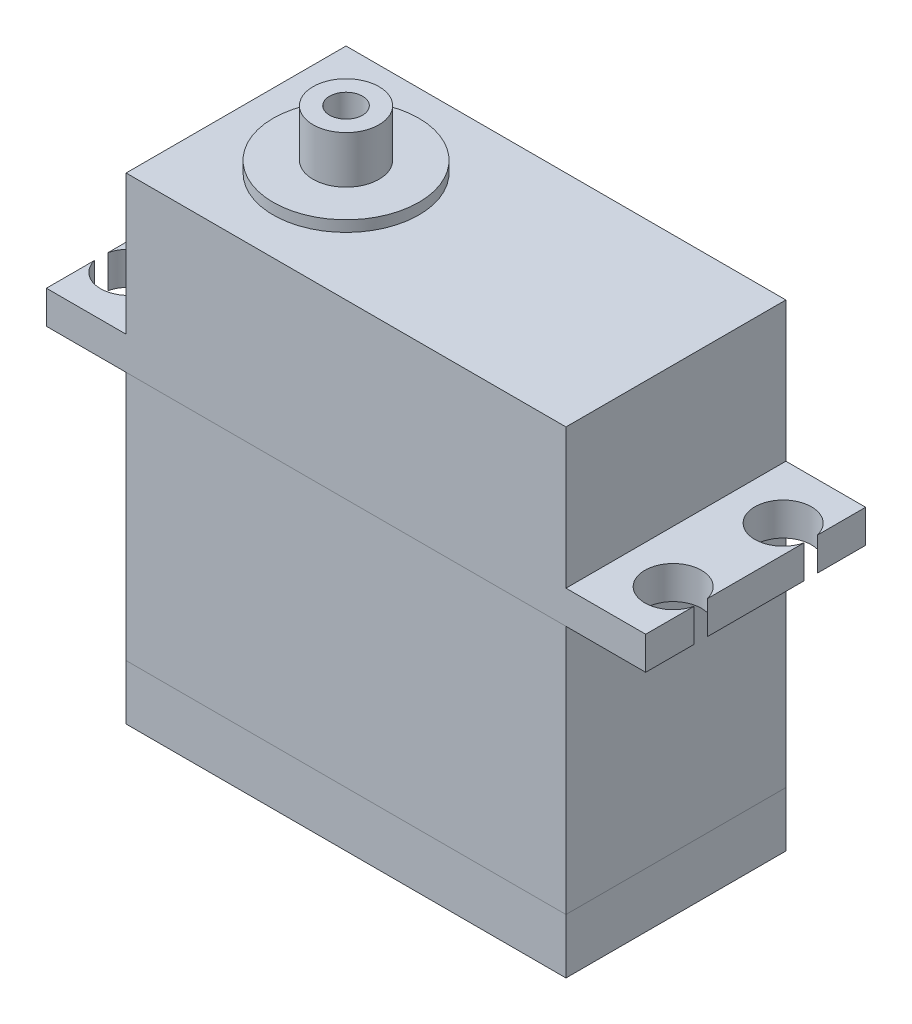
SolidWorks part; units mm, degrees
material "Nylon 101"
ref_plane "Front Plane" through (0, 0, 0) normal (0, 0, 1) x (1, 0, 0)
ref_plane "Top Plane" through (0, 0, 0) normal (0, 1, 0) x (1, 0, 0)
ref_plane "Right Plane" through (0, 0, 0) normal (1, 0, 0) x (0, 0, -1)
sketch "Sketch1" plane through (0, 0, 0) normal (0, 1, 0) x (1, 0, 0)
  line L1 (0, 0) -> (40, 0)
  line L2 (0, 0) -> (0, 20)
  line L3 (0, 20) -> (40, 20)
  line L4 (40, 0) -> (40, 20)
  dimension "D1" = 20
  dimension "D2" = 40
extrude "Boss-Extrude1" add sketch "Sketch1" along normal blind 12.7
sketch "Sketch2" plane through (0, 0, 0) normal (0, -1, 0) x (1, 0, 0)
  line L0 (40, -20) -> (0, -20) construction
  line L1 (-7.25, 0) -> (47.25, 0)
  line L2 (-7.25, 0) -> (-7.25, -20)
  line L3 (-7.25, -20) -> (47.25, -20)
  line L4 (47.25, 0) -> (47.25, -20)
  line L6 (0, 0) -> (40, 0) construction
  point P8 (20, 0)
  point P9 (20, 0)
  dimension "D1" = 54.5
extrude "Boss-Extrude2" add sketch "Sketch2" along normal blind 3
sketch "Sketch3" plane through (0, -3, 0) normal (0, -1, 0) x (1, 0, 0)
  line L4 (0, 0) -> (0, -20)
  line L5 (40, 0) -> (0, 0)
  line L6 (40, -20) -> (40, 0)
  line L7 (0, -20) -> (40, -20)
  line L8 (0, 0) -> (0, -20)
  line L9 (40, 0) -> (0, 0)
  line L10 (40, -20) -> (40, 0)
  line L11 (0, -20) -> (40, -20)
  dimension "D1" = 0
extrude "Boss-Extrude3" add sketch "Sketch3" along normal blind 22.7 separate body
sketch "Sketch4" plane through (0, -25.7, 0) normal (0, -1, 0) x (1, 0, 0)
  line L4 (0, -20) -> (40, -20)
  line L5 (40, -20) -> (40, 0)
  line L6 (40, 0) -> (0, 0)
  line L7 (0, 0) -> (0, -20)
  line L8 (0, -20) -> (40, -20)
  line L9 (40, -20) -> (40, 0)
  line L10 (40, 0) -> (0, 0)
  line L11 (0, 0) -> (0, -20)
  dimension "D1" = 0
extrude "Boss-Extrude5" add sketch "Sketch4" along normal blind 5 separate body
sketch "Sketch5" plane through (0, 12.7, 0) normal (0, 1, 0) x (1, 0, 0)
  line L0 (-7.25, 0) -> (-7.25, 20) construction
  circle A0 centre (10, 10) radius 6.625
  point P4 (-7.25, 10)
  dimension "D1" = 13.25
  dimension "D2" = 17.25
extrude "Boss-Extrude6" add sketch "Sketch5" along normal blind 1
sketch "Sketch6" plane through (0, 13.7, 0) normal (0, 1, 0) x (1, 0, 0)
  circle A0 centre (10, 10) radius 3
  circle A1 centre (10, 10) radius 6.625
  circle A2 centre (10, 10) radius 6.625 construction
  dimension "D2" = 6
  dimension "D1" = 0
extrude "Boss-Extrude7" add sketch "Sketch6" along normal blind 4.3 separate body
sketch "Sketch7" plane through (0, 0, 0) normal (0, 1, 0) x (1, 0, 0)
  line L0 (40, 20) -> (0, 20) construction
  line L1 (-4.75, 15) -> (44.75, 15) construction
  line L2 (-4.75, 15) -> (-4.75, 5) construction
  line L3 (-4.75, 5) -> (44.75, 5) construction
  line L4 (44.75, 15) -> (44.75, 5) construction
  line L5 (20, 20) -> (20, 0) construction
  line L6 (0, 0) -> (40, 0) construction
  circle A0 centre (-4.75, 5) radius 2.575
  circle A1 centre (-4.75, 15) radius 2.575
  circle A2 centre (44.75, 15) radius 2.575
  circle A3 centre (44.75, 5) radius 2.575
  point P10 (20, 20)
  point P11 (20, 15)
  point P16 (20, 10)
  point P17 (44.75, 10)
  dimension "D3" = 5.15
  dimension "D1" = 49.5
  dimension "D2" = 10
extrude "Cut-Extrude1" cut sketch "Sketch7" against normal up to next (3 mm away)
sketch "Sketch9" plane through (0, 18, 0) normal (0, 1, 0) x (1, 0, 0)
  circle A0 centre (10, 10) radius 1.5
  dimension "D1" = 3
extrude "Cut-Extrude3" cut sketch "Sketch9" against normal blind 4
chamfer "Chamfer1" [suppressed] distance 0.2 angle 45
sketch "Sketch10" [suppressed] plane through (40, 0, 0) normal (1, 0, 0) x (0, 0, -1)
  line L1 (7, -25.7) -> (13, -25.7)
  line L2 (7, -25.7) -> (7, -28.7)
  line L3 (7, -28.7) -> (13, -28.7)
  line L4 (13, -25.7) -> (13, -28.7)
  line L5 (20, -25.7) -> (0, -25.7) construction
  point P9 (10, -25.7)
  point P10 (10, -25.7)
  dimension "D1" = 3
  dimension "D2" = 6
extrude "Boss-Extrude8" [suppressed] add sketch "Sketch10" against normal blind 5 from surface separate body starting at face at (0, -28.2, -10)
sketch "Sketch8" [suppressed] plane through (0, 18, 0) normal (0, 1, 0) x (1, 0, 0)
  line L0 (10, 10) -> (10, 13) construction
  line L1 (9.675, 13) -> (10.325, 13)
  line L2 (10.325, 13) -> (10, 12.7)
  line L3 (10, 12.7) -> (9.675, 13)
  line L4 (10.6715, 12.6152) -> (10.4313, 12.9866)
  line L5 (10.4313, 12.9866) -> (11.0609, 12.8249)
  line L6 (11.0609, 12.8249) -> (10.6715, 12.6152)
  line L7 (11.3007, 12.366) -> (11.1605, 12.7855)
  line L8 (11.1605, 12.7855) -> (11.7301, 12.4724)
  line L9 (11.7301, 12.4724) -> (11.3007, 12.366)
  line L10 (11.8483, 11.9682) -> (11.8167, 12.4094)
  line L11 (11.8167, 12.4094) -> (12.2906, 11.9644)
  line L12 (12.2906, 11.9644) -> (11.8483, 11.9682)
  line L13 (12.2797, 11.4467) -> (12.3588, 11.8819)
  line L14 (12.3588, 11.8819) -> (12.7071, 11.3331)
  line L15 (12.7071, 11.3331) -> (12.2797, 11.4467)
  line L16 (12.5679, 10.8343) -> (12.7527, 11.2361)
  line L17 (12.7527, 11.2361) -> (12.9536, 10.618)
  line L18 (12.9536, 10.618) -> (12.5679, 10.8343)
  line L19 (12.6947, 10.1695) -> (12.9737, 10.5127)
  line L20 (12.9737, 10.5127) -> (13.0145, 9.864)
  line L21 (13.0145, 9.864) -> (12.6947, 10.1695)
  line L22 (12.6522, 9.4941) -> (13.0078, 9.7571)
  line L23 (13.0078, 9.7571) -> (12.886, 9.1186)
  line L24 (12.886, 9.1186) -> (12.6522, 9.4941)
  line L25 (12.443, 8.8504) -> (12.8529, 9.0167)
  line L26 (12.8529, 9.0167) -> (12.5761, 8.4286)
  line L27 (12.5761, 8.4286) -> (12.443, 8.8504)
  line L28 (12.0804, 8.279) -> (12.5187, 8.3381)
  line L29 (12.5187, 8.3381) -> (12.1044, 7.8373)
  line L30 (12.1044, 7.8373) -> (12.0804, 8.279)
  line L31 (11.587, 7.8157) -> (12.0263, 7.764)
  line L32 (12.0263, 7.764) -> (11.5004, 7.3819)
  line L33 (11.5004, 7.3819) -> (11.587, 7.8157)
  line L34 (10.9939, 7.4896) -> (11.4066, 7.3303)
  line L35 (11.4066, 7.3303) -> (10.8022, 7.091)
  line L36 (10.8022, 7.091) -> (10.9939, 7.4896)
  line L37 (10.3384, 7.3213) -> (10.6984, 7.0644)
  line L38 (10.6984, 7.0644) -> (10.0536, 6.9829)
  line L39 (10.0536, 6.9829) -> (10.3384, 7.3213)
  line L40 (9.6616, 7.3213) -> (9.9464, 6.9829)
  line L41 (9.9464, 6.9829) -> (9.3016, 7.0644)
  line L42 (9.3016, 7.0644) -> (9.6616, 7.3213)
  line L43 (9.0061, 7.4896) -> (9.1978, 7.091)
  line L44 (9.1978, 7.091) -> (8.5934, 7.3303)
  line L45 (8.5934, 7.3303) -> (9.0061, 7.4896)
  line L46 (8.413, 7.8157) -> (8.4996, 7.3819)
  line L47 (8.4996, 7.3819) -> (7.9737, 7.764)
  line L48 (7.9737, 7.764) -> (8.413, 7.8157)
  line L49 (7.9196, 8.279) -> (7.8956, 7.8373)
  line L50 (7.8956, 7.8373) -> (7.4813, 8.3381)
  line L51 (7.4813, 8.3381) -> (7.9196, 8.279)
  line L52 (7.557, 8.8504) -> (7.4239, 8.4286)
  line L53 (7.4239, 8.4286) -> (7.1471, 9.0167)
  line L54 (7.1471, 9.0167) -> (7.557, 8.8504)
  line L55 (7.3478, 9.4941) -> (7.114, 9.1186)
  line L56 (7.114, 9.1186) -> (6.9922, 9.7571)
  line L57 (6.9922, 9.7571) -> (7.3478, 9.4941)
  line L58 (7.3053, 10.1695) -> (6.9855, 9.864)
  line L59 (6.9855, 9.864) -> (7.0263, 10.5127)
  line L60 (7.0263, 10.5127) -> (7.3053, 10.1695)
  line L61 (7.4321, 10.8343) -> (7.0464, 10.618)
  line L62 (7.0464, 10.618) -> (7.2473, 11.2361)
  line L63 (7.2473, 11.2361) -> (7.4321, 10.8343)
  line L64 (7.7203, 11.4467) -> (7.2929, 11.3331)
  line L65 (7.2929, 11.3331) -> (7.6412, 11.8819)
  line L66 (7.6412, 11.8819) -> (7.7203, 11.4467)
  line L67 (8.1517, 11.9682) -> (7.7094, 11.9644)
  line L68 (7.7094, 11.9644) -> (8.1833, 12.4094)
  line L69 (8.1833, 12.4094) -> (8.1517, 11.9682)
  line L70 (8.6993, 12.366) -> (8.2699, 12.4724)
  line L71 (8.2699, 12.4724) -> (8.8395, 12.7855)
  line L72 (8.8395, 12.7855) -> (8.6993, 12.366)
  line L73 (9.3285, 12.6152) -> (8.9391, 12.8249)
  line L74 (8.9391, 12.8249) -> (9.5687, 12.9866)
  line L75 (9.5687, 12.9866) -> (9.3285, 12.6152)
  circle A0 centre (10, 10) radius 3 construction
  point P7 (10, 13)
  point P84 (10, 10)
  dimension "D1" = 0.3
  dimension "D2" = 0.65
  dimension "D3" = 25
extrude "Cut-Extrude2" [suppressed] cut sketch "Sketch8" against normal blind 3.3
sketch "Sketch11" [suppressed] plane through (0, 12.7, 0) normal (0, 1, 0) x (1, 0, 0)
  line L0 (20, 20) -> (20, 0) construction
  line L1 (40, 20) -> (0, 20) construction
  line L2 (0, 0) -> (40, 0) construction
  line L3 (0, 10) -> (40, 10) construction
  line L4 (0, 20) -> (0, 0) construction
  line L5 (40, 0) -> (40, 20) construction
  line L6 (35.8, 2.1) -> (35.8, 0)
  line L7 (35.8, 0) -> (40, 0)
  line L9 (37.9, 4.2) -> (40, 4.2)
  line L10 (40, 0) -> (40, 20) construction
  line L11 (40, 4.2) -> (40, 0)
  line L12 (37.9, 15.8) -> (40, 15.8)
  line L13 (40, 15.8) -> (40, 20)
  line L14 (35.8, 20) -> (40, 20)
  line L15 (35.8, 17.9) -> (35.8, 20)
  line L16 (2.1, 4.2) -> (0, 4.2)
  line L17 (0, 4.2) -> (0, 0)
  line L18 (4.2, 0) -> (0, 0)
  line L19 (4.2, 2.1) -> (4.2, 0)
  line L20 (4.2, 17.9) -> (4.2, 20)
  line L21 (4.2, 20) -> (0, 20)
  line L22 (0, 15.8) -> (0, 20)
  line L23 (2.1, 15.8) -> (0, 15.8)
  arc A0 (37.9, 4.2) -> (35.8, 2.1) centre (37.9, 2.1) ccw
  arc A1 (37.9, 15.8) -> (35.8, 17.9) centre (37.9, 17.9) cw
  arc A2 (2.1, 4.2) -> (4.2, 2.1) centre (2.1, 2.1) cw
  arc A3 (2.1, 15.8) -> (4.2, 17.9) centre (2.1, 17.9) ccw
  dimension "D1" = 4.2
extrude "Cut-Extrude4" [suppressed] cut sketch "Sketch11" against normal blind 1.75
sketch "Sketch13" [suppressed] plane through (0, -30.7, 0) normal (0, -1, 0) x (1, 0, 0)
  line L0 (37.9, -15.8) -> (40, -15.8) construction
  line L1 (40, -15.8) -> (40, -20) construction
  line L2 (40, -20) -> (35.8, -20) construction
  line L3 (35.8, -20) -> (35.8, -17.9) construction
  line L4 (35.8, -2.1) -> (35.8, 0) construction
  line L5 (35.8, 0) -> (40, 0) construction
  line L6 (40, 0) -> (40, -4.2) construction
  line L7 (40, -4.2) -> (37.9, -4.2) construction
  line L8 (2.1, -4.2) -> (0, -4.2) construction
  line L9 (0, -4.2) -> (0, 0) construction
  line L10 (0, 0) -> (4.2, 0) construction
  line L11 (4.2, 0) -> (4.2, -2.1) construction
  line L12 (4.2, -17.9) -> (4.2, -20) construction
  line L13 (4.2, -20) -> (0, -20) construction
  line L14 (0, -20) -> (0, -15.8) construction
  line L15 (0, -15.8) -> (2.1, -15.8) construction
  line L16 (37.9, -15.8) -> (40, -15.8)
  line L17 (40, -15.8) -> (40, -20)
  line L18 (40, -20) -> (35.8, -20)
  line L19 (35.8, -20) -> (35.8, -17.9)
  line L20 (35.8, -2.1) -> (35.8, 0)
  line L21 (35.8, 0) -> (40, 0)
  line L22 (40, 0) -> (40, -4.2)
  line L23 (40, -4.2) -> (37.9, -4.2)
  line L24 (2.1, -4.2) -> (0, -4.2)
  line L25 (0, -4.2) -> (0, 0)
  line L26 (0, 0) -> (4.2, 0)
  line L27 (4.2, 0) -> (4.2, -2.1)
  line L28 (4.2, -17.9) -> (4.2, -20)
  line L29 (4.2, -20) -> (0, -20)
  line L30 (0, -20) -> (0, -15.8)
  line L31 (0, -15.8) -> (2.1, -15.8)
  arc A0 (37.9, -15.8) -> (35.8, -17.9) centre (37.9, -17.9) ccw construction
  arc A1 (35.8, -2.1) -> (37.9, -4.2) centre (37.9, -2.1) ccw construction
  arc A2 (2.1, -4.2) -> (4.2, -2.1) centre (2.1, -2.1) ccw construction
  arc A3 (4.2, -17.9) -> (2.1, -15.8) centre (2.1, -17.9) ccw construction
  arc A4 (37.9, -15.8) -> (35.8, -17.9) centre (37.9, -17.9) ccw
  arc A5 (35.8, -2.1) -> (37.9, -4.2) centre (37.9, -2.1) ccw
  arc A6 (2.1, -4.2) -> (4.2, -2.1) centre (2.1, -2.1) ccw
  arc A7 (4.2, -17.9) -> (2.1, -15.8) centre (2.1, -17.9) ccw
extrude "Cut-Extrude6" [suppressed] cut sketch "Sketch13" against normal blind 1.75
sketch "Sketch12" [suppressed] plane through (0, 12.7, 0) normal (0, 1, 0) x (1, 0, 0)
  line L0 (0, 10) -> (40, 10) construction
  line L1 (0, 15.8) -> (0, 4.2) construction
  line L2 (40, 4.2) -> (40, 15.8) construction
  line L3 (35.8, 20) -> (4.2, 20) construction
  line L4 (13, 20) -> (27, 20)
  line L5 (13, 20) -> (13, 18.75)
  line L6 (13, 18.75) -> (27, 18.75)
  line L7 (27, 20) -> (27, 18.75)
  line L8 (13, 1.25) -> (27, 1.25)
  line L9 (27, 0) -> (27, 1.25)
  line L10 (13, 0) -> (27, 0)
  line L11 (13, 0) -> (13, 1.25)
  point P12 (20, 20)
  point P13 (20, 10)
  dimension "D1" = 1.25
  dimension "D2" = 14
extrude "Cut-Extrude5" [suppressed] cut sketch "Sketch12" against normal blind 1.25
sketch "Sketch14" [suppressed] plane through (0, -30.7, 0) normal (0, -1, 0) x (1, 0, 0)
  line L0 (13, -20) -> (13, -18.75) construction
  line L1 (13, -18.75) -> (27, -18.75) construction
  line L2 (27, -18.75) -> (27, -20) construction
  line L3 (27, -20) -> (13, -20) construction
  line L4 (13, -1.25) -> (13, 0) construction
  line L5 (13, 0) -> (27, 0) construction
  line L6 (27, 0) -> (27, -1.25) construction
  line L7 (27, -1.25) -> (13, -1.25) construction
  line L8 (13, -20) -> (13, -18.75)
  line L9 (13, -18.75) -> (27, -18.75)
  line L10 (27, -18.75) -> (27, -20)
  line L11 (27, -20) -> (13, -20)
  line L12 (13, -1.25) -> (13, 0)
  line L13 (13, 0) -> (27, 0)
  line L14 (27, 0) -> (27, -1.25)
  line L15 (27, -1.25) -> (13, -1.25)
extrude "Cut-Extrude7" [suppressed] cut sketch "Sketch14" against normal blind 1.25
chamfer "Chamfer2" [suppressed] distance 1.25 angle 45
chamfer "Chamfer3" [suppressed] distance 1.25 angle 45
fillet "Fillet1" [suppressed] radius 1.25
chamfer "Chamfer5" [suppressed] distance 0.3 angle 45
fillet "Fillet2" [suppressed] radius 1.25
chamfer "Chamfer6" [suppressed] distance 0.3 angle 45
fillet "Fillet3" [suppressed] radius 1
fillet "Fillet4" [suppressed] radius 1
fillet "Fillet5" [suppressed] radius 1
sketch "Sketch15" [suppressed] plane through (0, 10.95, 0) normal (0, 1, 0) x (1, 0, 0)
  line L0 (40, 15.8) -> (40, 19) construction
  line L1 (39, 20) -> (35.8, 20) construction
  line L2 (35.8, 20) -> (35.8, 17.9) construction
  line L3 (37.9, 15.8) -> (40, 15.8) construction
  line L4 (4.2, 20) -> (1, 20) construction
  line L5 (0, 19) -> (0, 15.8) construction
  line L6 (0, 15.8) -> (2.1, 15.8) construction
  line L7 (4.2, 17.9) -> (4.2, 20) construction
  line L8 (0, 4.2) -> (0, 1) construction
  line L9 (1, 0) -> (4.2, 0) construction
  line L10 (4.2, 0) -> (4.2, 2.1) construction
  line L11 (2.1, 4.2) -> (0, 4.2) construction
  line L12 (35.8, 0) -> (39, 0) construction
  line L13 (40, 1) -> (40, 4.2) construction
  line L14 (40, 4.2) -> (37.9, 4.2) construction
  line L15 (35.8, 2.1) -> (35.8, 0) construction
  line L16 (40, 15.8) -> (40, 19) construction
  line L17 (39, 20) -> (35.8, 20) construction
  line L18 (35.8, 20) -> (35.8, 17.9) construction
  line L19 (37.9, 15.8) -> (40, 15.8) construction
  line L20 (4.2, 20) -> (1, 20) construction
  line L21 (0, 19) -> (0, 15.8) construction
  line L22 (0, 15.8) -> (2.1, 15.8) construction
  line L23 (4.2, 17.9) -> (4.2, 20) construction
  line L24 (0, 4.2) -> (0, 1) construction
  line L25 (1, 0) -> (4.2, 0) construction
  line L26 (4.2, 0) -> (4.2, 2.1) construction
  line L27 (2.1, 4.2) -> (0, 4.2) construction
  line L28 (35.8, 0) -> (39, 0) construction
  line L29 (40, 1) -> (40, 4.2) construction
  line L30 (40, 4.2) -> (37.9, 4.2) construction
  line L31 (35.8, 2.1) -> (35.8, 0) construction
  arc A0 (40, 19) -> (39, 20) centre (39, 19) ccw construction
  arc A1 (35.8, 17.9) -> (37.9, 15.8) centre (37.9, 17.9) ccw construction
  arc A2 (1, 20) -> (0, 19) centre (1, 19) ccw construction
  arc A3 (2.1, 15.8) -> (4.2, 17.9) centre (2.1, 17.9) ccw construction
  arc A4 (0, 1) -> (1, 0) centre (1, 1) ccw construction
  arc A5 (4.2, 2.1) -> (2.1, 4.2) centre (2.1, 2.1) ccw construction
  arc A6 (39, 0) -> (40, 1) centre (39, 1) ccw construction
  arc A7 (37.9, 4.2) -> (35.8, 2.1) centre (37.9, 2.1) ccw construction
  arc A8 (40, 19) -> (39, 20) centre (39, 19) ccw construction
  arc A9 (35.8, 17.9) -> (37.9, 15.8) centre (37.9, 17.9) ccw construction
  arc A10 (1, 20) -> (0, 19) centre (1, 19) ccw construction
  arc A11 (2.1, 15.8) -> (4.2, 17.9) centre (2.1, 17.9) ccw construction
  arc A12 (0, 1) -> (1, 0) centre (1, 1) ccw construction
  arc A13 (4.2, 2.1) -> (2.1, 4.2) centre (2.1, 2.1) ccw construction
  arc A14 (39, 0) -> (40, 1) centre (39, 1) ccw construction
  arc A15 (37.9, 4.2) -> (35.8, 2.1) centre (37.9, 2.1) ccw construction
  circle A16 centre (2.1, 2.1) radius 1.875
  circle A17 centre (2.1, 17.9) radius 1.875
  circle A18 centre (37.9, 17.9) radius 1.875
  circle A19 centre (37.9, 2.1) radius 1.875
  dimension "D1" = 3.75
extrude "Boss-Extrude10" [suppressed] add sketch "Sketch15" along normal blind 1.25 separate body
sketch "Sketch16" [suppressed] plane through (0, -28.95, 0) normal (0, -1, 0) x (1, 0, 0)
  circle A0 centre (2.1, -2.1) radius 1.875 construction
  circle A1 centre (37.9, -2.1) radius 1.875 construction
  circle A2 centre (37.9, -17.9) radius 1.875 construction
  circle A3 centre (2.1, -17.9) radius 1.875 construction
  circle A4 centre (2.1, -2.1) radius 1.875
  circle A5 centre (37.9, -2.1) radius 1.875
  circle A6 centre (37.9, -17.9) radius 1.875
  circle A7 centre (2.1, -17.9) radius 1.875
extrude "Boss-Extrude12" [suppressed] add sketch "Sketch16" along normal blind 1.25 separate body
chamfer "Chamfer8" [suppressed] distance 0.15 angle 45
sketch "Sketch18" [suppressed] plane through (0, 12.2, 0) normal (0, 1, 0) x (1, 0, 0)
  line L0 (0.3, 10) -> (39.7, 10) construction
  line L1 (0.3, 15.5) -> (0.3, 4.5) construction
  line L2 (39.7, 4.5) -> (39.7, 15.5) construction
  line L3 (20, 18.75) -> (20, 1.25) construction
  line L4 (14.25, 18.75) -> (25.75, 18.75) construction
  line L5 (25.75, 1.25) -> (14.25, 1.25) construction
  line L6 (2.7351, 3.2) -> (3.3702, 2.1)
  line L7 (3.3702, 17.9) -> (2.7351, 19)
  line L8 (2.7351, 19) -> (1.4649, 19)
  line L9 (1.4649, 19) -> (0.8298, 17.9)
  line L10 (0.8298, 17.9) -> (1.4649, 16.8)
  line L11 (1.4649, 16.8) -> (2.7351, 16.8)
  line L12 (2.7351, 16.8) -> (3.3702, 17.9)
  line L13 (1.4649, 3.2) -> (2.7351, 3.2)
  line L14 (0.8298, 2.1) -> (1.4649, 3.2)
  line L15 (1.4649, 1) -> (0.8298, 2.1)
  line L16 (2.7351, 1) -> (1.4649, 1)
  line L17 (3.3702, 2.1) -> (2.7351, 1)
  line L18 (38.5351, 3.2) -> (37.2649, 3.2)
  line L19 (39.1702, 2.1) -> (38.5351, 3.2)
  line L20 (38.5351, 1) -> (39.1702, 2.1)
  line L21 (37.2649, 1) -> (38.5351, 1)
  line L22 (36.6298, 2.1) -> (37.2649, 1)
  line L23 (37.2649, 3.2) -> (36.6298, 2.1)
  line L24 (37.2649, 16.8) -> (36.6298, 17.9)
  line L25 (38.5351, 16.8) -> (37.2649, 16.8)
  line L26 (39.1702, 17.9) -> (38.5351, 16.8)
  line L27 (38.5351, 19) -> (39.1702, 17.9)
  line L28 (37.2649, 19) -> (38.5351, 19)
  line L29 (36.6298, 17.9) -> (37.2649, 19)
  circle A1 centre (2.1, 17.9) radius 1.1 construction
  circle A2 centre (2.1, 17.9) radius 1.875
  circle A3 centre (2.1, 17.9) radius 1.875 construction
  dimension "D1" = 0
  dimension "D2" = 2.2
extrude "Cut-Extrude8" [suppressed] cut sketch "Sketch18" against normal blind 1.22
sketch "Sketch19" [suppressed] plane through (0, -30.2, 0) normal (0, -1, 0) x (1, 0, 0)
  line L0 (37.2649, -16.8) -> (38.5351, -16.8) construction
  line L1 (38.5351, -16.8) -> (39.1702, -17.9) construction
  line L2 (39.1702, -17.9) -> (38.5351, -19) construction
  line L3 (38.5351, -19) -> (37.2649, -19) construction
  line L4 (37.2649, -19) -> (36.6298, -17.9) construction
  line L5 (36.6298, -17.9) -> (37.2649, -16.8) construction
  line L6 (39.1702, -2.1) -> (38.5351, -3.2) construction
  line L7 (38.5351, -3.2) -> (37.2649, -3.2) construction
  line L8 (37.2649, -3.2) -> (36.6298, -2.1) construction
  line L9 (36.6298, -2.1) -> (37.2649, -1) construction
  line L10 (37.2649, -1) -> (38.5351, -1) construction
  line L11 (38.5351, -1) -> (39.1702, -2.1) construction
  line L12 (2.7351, -3.2) -> (1.4649, -3.2) construction
  line L13 (1.4649, -3.2) -> (0.8298, -2.1) construction
  line L14 (0.8298, -2.1) -> (1.4649, -1) construction
  line L15 (1.4649, -1) -> (2.7351, -1) construction
  line L16 (2.7351, -1) -> (3.3702, -2.1) construction
  line L17 (3.3702, -2.1) -> (2.7351, -3.2) construction
  line L18 (2.7351, -16.8) -> (3.3702, -17.9) construction
  line L19 (3.3702, -17.9) -> (2.7351, -19) construction
  line L20 (2.7351, -19) -> (1.4649, -19) construction
  line L21 (1.4649, -19) -> (0.8298, -17.9) construction
  line L22 (0.8298, -17.9) -> (1.4649, -16.8) construction
  line L23 (1.4649, -16.8) -> (2.7351, -16.8) construction
  line L24 (37.2649, -16.8) -> (38.5351, -16.8)
  line L25 (38.5351, -16.8) -> (39.1702, -17.9)
  line L26 (39.1702, -17.9) -> (38.5351, -19)
  line L27 (38.5351, -19) -> (37.2649, -19)
  line L28 (37.2649, -19) -> (36.6298, -17.9)
  line L29 (36.6298, -17.9) -> (37.2649, -16.8)
  line L30 (39.1702, -2.1) -> (38.5351, -3.2)
  line L31 (38.5351, -3.2) -> (37.2649, -3.2)
  line L32 (37.2649, -3.2) -> (36.6298, -2.1)
  line L33 (36.6298, -2.1) -> (37.2649, -1)
  line L34 (37.2649, -1) -> (38.5351, -1)
  line L35 (38.5351, -1) -> (39.1702, -2.1)
  line L36 (2.7351, -3.2) -> (1.4649, -3.2)
  line L37 (1.4649, -3.2) -> (0.8298, -2.1)
  line L38 (0.8298, -2.1) -> (1.4649, -1)
  line L39 (1.4649, -1) -> (2.7351, -1)
  line L40 (2.7351, -1) -> (3.3702, -2.1)
  line L41 (3.3702, -2.1) -> (2.7351, -3.2)
  line L42 (2.7351, -16.8) -> (3.3702, -17.9)
  line L43 (3.3702, -17.9) -> (2.7351, -19)
  line L44 (2.7351, -19) -> (1.4649, -19)
  line L45 (1.4649, -19) -> (0.8298, -17.9)
  line L46 (0.8298, -17.9) -> (1.4649, -16.8)
  line L47 (1.4649, -16.8) -> (2.7351, -16.8)
extrude "Cut-Extrude9" [suppressed] cut sketch "Sketch19" against normal blind 1.22
sketch "Sketch23" [suppressed] plane through (0, 18, 0) normal (0, 1, 0) x (1, 0, 0)
  line L50 (11.0403, 12.8139) -> (10.6715, 12.6152)
  line L51 (10.6715, 12.6152) -> (10.444, 12.967)
  line L52 (10.3078, 12.9842) -> (10, 12.7)
  line L53 (10, 12.7) -> (9.6922, 12.9842)
  line L54 (9.556, 12.967) -> (9.3285, 12.6152)
  line L55 (9.3285, 12.6152) -> (8.9597, 12.8139)
  line L56 (8.8321, 12.7633) -> (8.6993, 12.366)
  line L57 (8.6993, 12.366) -> (8.2926, 12.4667)
  line L58 (8.1816, 12.3861) -> (8.1517, 11.9682)
  line L59 (8.1517, 11.9682) -> (7.7328, 11.9646)
  line L60 (7.6453, 11.8589) -> (7.7203, 11.4467)
  line L61 (7.7203, 11.4467) -> (7.3154, 11.3391)
  line L62 (7.257, 11.2149) -> (7.4321, 10.8343)
  line L63 (7.4321, 10.8343) -> (7.0668, 10.6294)
  line L64 (7.0411, 10.4946) -> (7.3053, 10.1695)
  line L65 (7.3053, 10.1695) -> (7.0024, 9.8801)
  line L66 (7.011, 9.7432) -> (7.3478, 9.4941)
  line L67 (7.3478, 9.4941) -> (7.1264, 9.1384)
  line L68 (7.1688, 9.008) -> (7.557, 8.8504)
  line L69 (7.557, 8.8504) -> (7.4309, 8.4509)
  line L70 (7.5044, 8.335) -> (7.9196, 8.279)
  line L71 (7.9196, 8.279) -> (7.8969, 7.8606)
  line L72 (7.9969, 7.7667) -> (8.413, 7.8157)
  line L73 (8.413, 7.8157) -> (8.495, 7.4048)
  line L74 (8.6152, 7.3387) -> (9.0061, 7.4896)
  line L75 (9.0061, 7.4896) -> (9.1877, 7.1121)
  line L76 (9.3206, 7.078) -> (9.6616, 7.3213)
  line L77 (9.6616, 7.3213) -> (9.9314, 7.0008)
  line L78 (10.0686, 7.0008) -> (10.3384, 7.3213)
  line L79 (10.3384, 7.3213) -> (10.6794, 7.078)
  line L80 (10.8123, 7.1121) -> (10.9939, 7.4896)
  line L81 (10.9939, 7.4896) -> (11.3848, 7.3387)
  line L82 (11.505, 7.4048) -> (11.587, 7.8157)
  line L83 (11.587, 7.8157) -> (12.0031, 7.7667)
  line L84 (12.1031, 7.8606) -> (12.0804, 8.279)
  line L85 (12.0804, 8.279) -> (12.4956, 8.335)
  line L86 (12.5691, 8.4509) -> (12.443, 8.8504)
  line L87 (12.443, 8.8504) -> (12.8312, 9.008)
  line L88 (12.8736, 9.1384) -> (12.6522, 9.4941)
  line L89 (12.6522, 9.4941) -> (12.989, 9.7432)
  line L90 (12.9976, 9.8801) -> (12.6947, 10.1695)
  line L91 (12.6947, 10.1695) -> (12.9589, 10.4946)
  line L92 (12.9332, 10.6294) -> (12.5679, 10.8343)
  line L93 (12.5679, 10.8343) -> (12.743, 11.2149)
  line L94 (12.6846, 11.3391) -> (12.2797, 11.4467)
  line L95 (12.2797, 11.4467) -> (12.3547, 11.8589)
  line L96 (12.2672, 11.9646) -> (11.8483, 11.9682)
  line L97 (11.8483, 11.9682) -> (11.8184, 12.3861)
  line L98 (11.7074, 12.4667) -> (11.3007, 12.366)
  line L99 (11.3007, 12.366) -> (11.1679, 12.7633)
  line L100 (11.0403, 12.8139) -> (10.6715, 12.6152)
  line L101 (10.6715, 12.6152) -> (10.444, 12.967)
  line L102 (10.3078, 12.9842) -> (10, 12.7)
  line L103 (10, 12.7) -> (9.6922, 12.9842)
  line L104 (9.556, 12.967) -> (9.3285, 12.6152)
  line L105 (9.3285, 12.6152) -> (8.9597, 12.8139)
  line L106 (8.8321, 12.7633) -> (8.6993, 12.366)
  line L107 (8.6993, 12.366) -> (8.2926, 12.4667)
  line L108 (8.1816, 12.3861) -> (8.1517, 11.9682)
  line L109 (8.1517, 11.9682) -> (7.7328, 11.9646)
  line L110 (7.6453, 11.8589) -> (7.7203, 11.4467)
  line L111 (7.7203, 11.4467) -> (7.3154, 11.3391)
  line L112 (7.257, 11.2149) -> (7.4321, 10.8343)
  line L113 (7.4321, 10.8343) -> (7.0668, 10.6294)
  line L114 (7.0411, 10.4946) -> (7.3053, 10.1695)
  line L115 (7.3053, 10.1695) -> (7.0024, 9.8801)
  line L116 (7.011, 9.7432) -> (7.3478, 9.4941)
  line L117 (7.3478, 9.4941) -> (7.1264, 9.1384)
  line L118 (7.1688, 9.008) -> (7.557, 8.8504)
  line L119 (7.557, 8.8504) -> (7.4309, 8.4509)
  line L120 (7.5044, 8.335) -> (7.9196, 8.279)
  line L121 (7.9196, 8.279) -> (7.8969, 7.8606)
  line L122 (7.9969, 7.7667) -> (8.413, 7.8157)
  line L123 (8.413, 7.8157) -> (8.495, 7.4048)
  line L124 (8.6152, 7.3387) -> (9.0061, 7.4896)
  line L125 (9.0061, 7.4896) -> (9.1877, 7.1121)
  line L126 (9.3206, 7.078) -> (9.6616, 7.3213)
  line L127 (9.6616, 7.3213) -> (9.9314, 7.0008)
  line L128 (10.0686, 7.0008) -> (10.3384, 7.3213)
  line L129 (10.3384, 7.3213) -> (10.6794, 7.078)
  line L130 (10.8123, 7.1121) -> (10.9939, 7.4896)
  line L131 (10.9939, 7.4896) -> (11.3848, 7.3387)
  line L132 (11.505, 7.4048) -> (11.587, 7.8157)
  line L133 (11.587, 7.8157) -> (12.0031, 7.7667)
  line L134 (12.1031, 7.8606) -> (12.0804, 8.279)
  line L135 (12.0804, 8.279) -> (12.4956, 8.335)
  line L136 (12.5691, 8.4509) -> (12.443, 8.8504)
  line L137 (12.443, 8.8504) -> (12.8312, 9.008)
  line L138 (12.8736, 9.1384) -> (12.6522, 9.4941)
  line L139 (12.6522, 9.4941) -> (12.989, 9.7432)
  line L140 (12.9976, 9.8801) -> (12.6947, 10.1695)
  line L141 (12.6947, 10.1695) -> (12.9589, 10.4946)
  line L142 (12.9332, 10.6294) -> (12.5679, 10.8343)
  line L143 (12.5679, 10.8343) -> (12.743, 11.2149)
  line L144 (12.6846, 11.3391) -> (12.2797, 11.4467)
  line L145 (12.2797, 11.4467) -> (12.3547, 11.8589)
  line L146 (12.2672, 11.9646) -> (11.8483, 11.9682)
  line L147 (11.8483, 11.9682) -> (11.8184, 12.3861)
  line L148 (11.7074, 12.4667) -> (11.3007, 12.366)
  line L149 (11.3007, 12.366) -> (11.1679, 12.7633)
  arc A25 (10.444, 12.967) -> (10.3078, 12.9842) centre (10, 10) ccw
  arc A26 (9.6922, 12.9842) -> (9.556, 12.967) centre (10, 10) ccw
  arc A27 (8.9597, 12.8139) -> (8.8321, 12.7633) centre (10, 10) ccw
  arc A28 (8.2926, 12.4667) -> (8.1816, 12.3861) centre (10, 10) ccw
  arc A29 (7.7328, 11.9646) -> (7.6453, 11.8589) centre (10, 10) ccw
  arc A30 (7.3154, 11.3391) -> (7.257, 11.2149) centre (10, 10) ccw
  arc A31 (7.0668, 10.6294) -> (7.0411, 10.4946) centre (10, 10) ccw
  arc A32 (7.0024, 9.8801) -> (7.011, 9.7432) centre (10, 10) ccw
  arc A33 (7.1264, 9.1384) -> (7.1688, 9.008) centre (10, 10) ccw
  arc A34 (7.4309, 8.4509) -> (7.5044, 8.335) centre (10, 10) ccw
  arc A35 (7.8969, 7.8606) -> (7.9969, 7.7667) centre (10, 10) ccw
  arc A36 (8.495, 7.4048) -> (8.6152, 7.3387) centre (10, 10) ccw
  arc A37 (9.1877, 7.1121) -> (9.3206, 7.078) centre (10, 10) ccw
  arc A38 (9.9314, 7.0008) -> (10.0686, 7.0008) centre (10, 10) ccw
  arc A39 (10.6794, 7.078) -> (10.8123, 7.1121) centre (10, 10) ccw
  arc A40 (11.3848, 7.3387) -> (11.505, 7.4048) centre (10, 10) ccw
  arc A41 (12.0031, 7.7667) -> (12.1031, 7.8606) centre (10, 10) ccw
  arc A42 (12.4956, 8.335) -> (12.5691, 8.4509) centre (10, 10) ccw
  arc A43 (12.8312, 9.008) -> (12.8736, 9.1384) centre (10, 10) ccw
  arc A44 (12.989, 9.7432) -> (12.9976, 9.8801) centre (10, 10) ccw
  arc A45 (12.9589, 10.4946) -> (12.9332, 10.6294) centre (10, 10) ccw
  arc A46 (12.743, 11.2149) -> (12.6846, 11.3391) centre (10, 10) ccw
  arc A47 (12.3547, 11.8589) -> (12.2672, 11.9646) centre (10, 10) ccw
  arc A48 (11.8184, 12.3861) -> (11.7074, 12.4667) centre (10, 10) ccw
  arc A49 (11.1679, 12.7633) -> (11.0403, 12.8139) centre (10, 10) ccw
  arc A50 (10.444, 12.967) -> (10.3078, 12.9842) centre (10, 10) ccw
  arc A51 (9.6922, 12.9842) -> (9.556, 12.967) centre (10, 10) ccw
  arc A52 (8.9597, 12.8139) -> (8.8321, 12.7633) centre (10, 10) ccw
  arc A53 (8.2926, 12.4667) -> (8.1816, 12.3861) centre (10, 10) ccw
  arc A54 (7.7328, 11.9646) -> (7.6453, 11.8589) centre (10, 10) ccw
  arc A55 (7.3154, 11.3391) -> (7.257, 11.2149) centre (10, 10) ccw
  arc A56 (7.0668, 10.6294) -> (7.0411, 10.4946) centre (10, 10) ccw
  arc A57 (7.0024, 9.8801) -> (7.011, 9.7432) centre (10, 10) ccw
  arc A58 (7.1264, 9.1384) -> (7.1688, 9.008) centre (10, 10) ccw
  arc A59 (7.4309, 8.4509) -> (7.5044, 8.335) centre (10, 10) ccw
  arc A60 (7.8969, 7.8606) -> (7.9969, 7.7667) centre (10, 10) ccw
  arc A61 (8.495, 7.4048) -> (8.6152, 7.3387) centre (10, 10) ccw
  arc A62 (9.1877, 7.1121) -> (9.3206, 7.078) centre (10, 10) ccw
  arc A63 (9.9314, 7.0008) -> (10.0686, 7.0008) centre (10, 10) ccw
  arc A64 (10.6794, 7.078) -> (10.8123, 7.1121) centre (10, 10) ccw
  arc A65 (11.3848, 7.3387) -> (11.505, 7.4048) centre (10, 10) ccw
  arc A66 (12.0031, 7.7667) -> (12.1031, 7.8606) centre (10, 10) ccw
  arc A67 (12.4956, 8.335) -> (12.5691, 8.4509) centre (10, 10) ccw
  arc A68 (12.8312, 9.008) -> (12.8736, 9.1384) centre (10, 10) ccw
  arc A69 (12.989, 9.7432) -> (12.9976, 9.8801) centre (10, 10) ccw
  arc A70 (12.9589, 10.4946) -> (12.9332, 10.6294) centre (10, 10) ccw
  arc A71 (12.743, 11.2149) -> (12.6846, 11.3391) centre (10, 10) ccw
  arc A72 (12.3547, 11.8589) -> (12.2672, 11.9646) centre (10, 10) ccw
  arc A73 (11.8184, 12.3861) -> (11.7074, 12.4667) centre (10, 10) ccw
  arc A74 (11.1679, 12.7633) -> (11.0403, 12.8139) centre (10, 10) ccw
  dimension "D1" = 0
chamfer "Chamfer9" [suppressed] distance 0.05 angle 45
chamfer "Chamfer10" [suppressed] distance 0.05 angle 45
